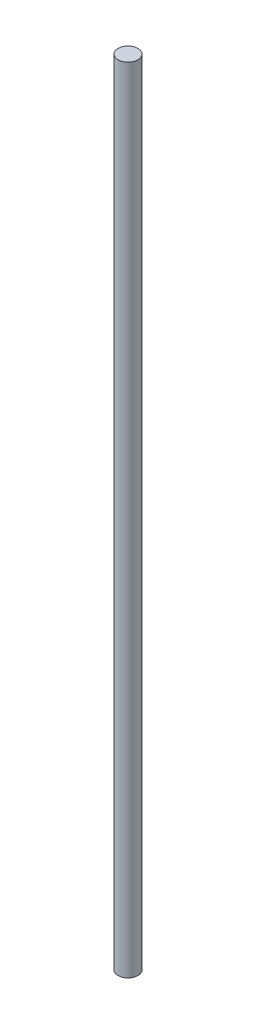
SolidWorks part; units mm, degrees
ref_plane "Front Plane" through (0, 0, 0) normal (0, 0, 1) x (1, 0, 0)
ref_plane "Top Plane" through (0, 0, 0) normal (0, 1, 0) x (1, 0, 0)
ref_plane "Right Plane" through (0, 0, 0) normal (1, 0, 0) x (0, 0, -1)
sketch "Sketch1" plane through (0, 0, 0) normal (0, 1, 0) x (1, 0, 0)
  circle A0 centre (0, 0) radius 2.5
  dimension "D1" = 5
extrude "Boss-Extrude1" add sketch "Sketch1" along normal blind 200
